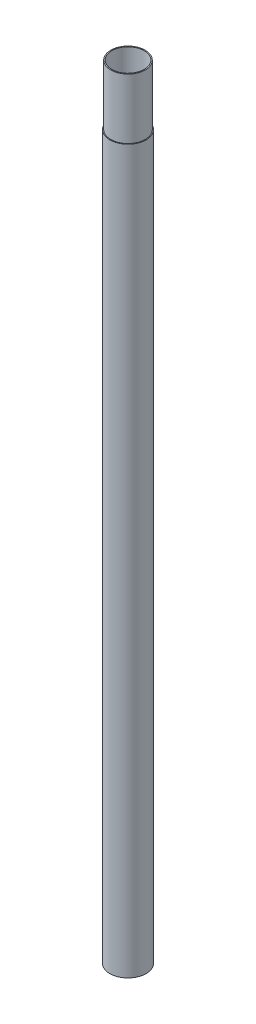
SolidWorks part; units mm, degrees
ref_plane "Front Plane" through (0, 0, 0) normal (0, 0, 1) x (1, 0, 0)
ref_plane "Top Plane" through (0, 0, 0) normal (0, 1, 0) x (1, 0, 0)
ref_plane "Right Plane" through (0, 0, 0) normal (1, 0, 0) x (0, 0, -1)
sketch "Sketch1" plane through (0, 0, 0) normal (0, 1, 0) x (1, 0, 0)
  circle A0 centre (0, 0) radius 15
  circle A1 centre (0, 0) radius 13.462
  circle A2 centre (0, 0) radius 15.875
  dimension "D1" = 30
  dimension "D2" = 31.75
  dimension "D3" = 2.413
extrude "Boss-Extrude1" add sketch "Sketch1" along normal blind 600 contours A0 A1 region at (-14.5757, 0, 0)
sketch "Sketch4" plane through (0, 600, 0) normal (0, 1, 0) x (1, 0, 0)
  circle A0 centre (0, 0) radius 14.3
  circle A1 centre (0, 0) radius 13.462 construction
  circle A2 centre (0, 0) radius 13.462
  circle M3 centre (0, 0) radius 13.462
  dimension "D1" = 28.6
extrude "Boss-Extrude5" add sketch "Sketch4" along normal blind 50 contours A0 M3 region at (-13.8955, 600, 0)
equation "\"bottomheight\"=600"
equation "\"D1@Boss-Extrude1\"=\"bottomheight\""
equation "\"topheight\"=50"
equation "\"D1@Boss-Extrude5\"=\"topheight\""
